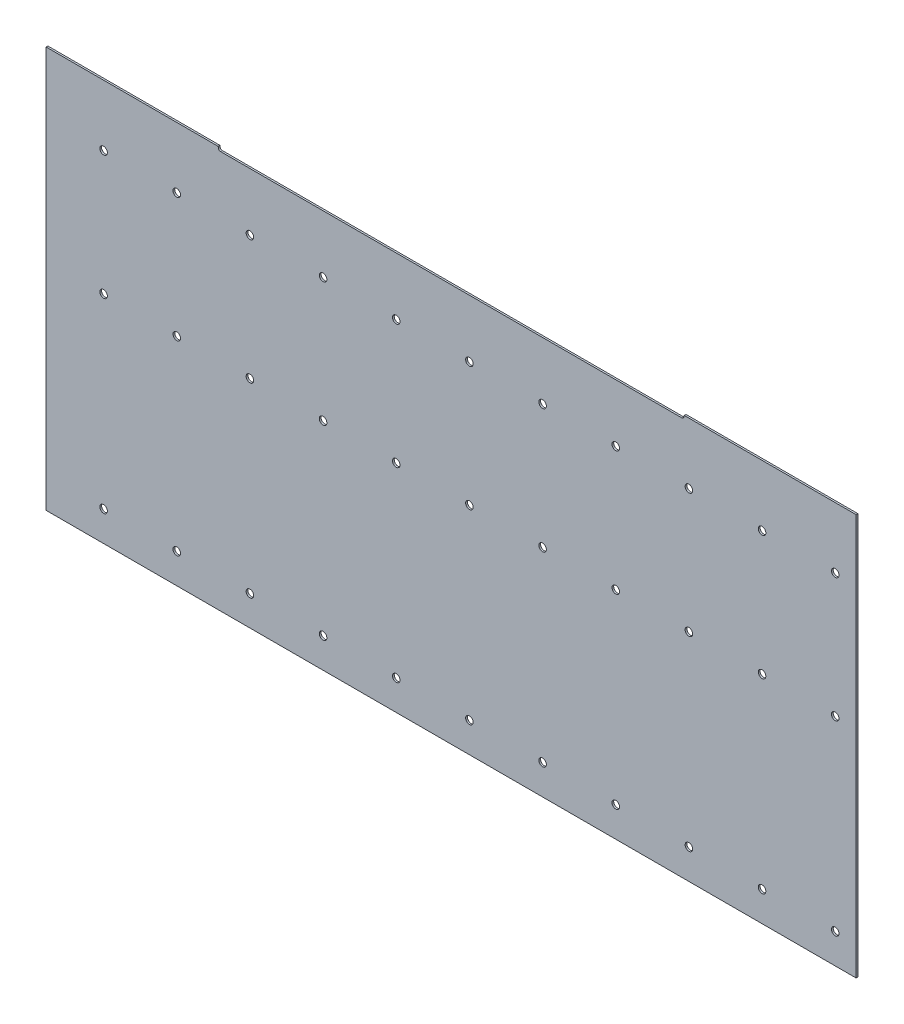
SolidWorks part; units mm, degrees
ref_plane "Plan de face" through (0, 0, 0) normal (0, 0, 1) x (1, 0, 0)
ref_plane "Plan de dessus" through (0, 0, 0) normal (0, 1, 0) x (1, 0, 0)
ref_plane "Plan de droite" through (0, 0, 0) normal (1, 0, 0) x (0, 0, -1)
sketch "Esquisse1" plane through (0, 0, 0) normal (0, 0, 1) x (1, 0, 0)
  line L5 (-182.65, -91) -> (182.65, -91)
  line L6 (-182.65, -91) -> (-182.65, 91)
  line L7 (-182.65, 91) -> (182.65, 91)
  line L8 (182.65, -91) -> (182.65, 91)
  line L9 (-182.65, -91) -> (182.65, 91) construction
  line L10 (-182.65, 91) -> (182.65, -91) construction
  point P0 (0, 0)
  dimension "D1" = 182
  dimension "D2" = 365.3
extrude "Boss.-Extru.1" add sketch "Esquisse1" along normal mid plane 0.7937
sketch "Esquisse2" plane through (0, 0, 0.3969) normal (0, 0, 1) x (1, 0, 0)
  line L0 (-156.75, 7) -> (-156.75, -77) construction
  line L1 (-182.65, 91) -> (-182.65, -91) construction
  line L2 (182.65, 91) -> (-182.65, 91) construction
  circle A0 centre (-156.75, 63) radius 1.7
  circle A1 centre (-156.75, 7) radius 1.7
  circle A2 centre (-156.75, -77) radius 1.7
  dimension "D3" = 3.4
  dimension "D4" = 28
  dimension "D5" = 84
  dimension "D6" = 168
  dimension "D1" = 25.9
  dimension "D2" = 25.9
extrude "Enlèv. mat.-Extru.1" cut sketch "Esquisse2" against normal blind 10
pattern_linear "Répétition linéaire1" count 11 spacing 33 along (1, 0, 0) of "Enlèv. mat.-Extru.1"
sketch "Esquisse3" plane through (0, 0, 0.3969) normal (0, 0, 1) x (1, 0, 0)
  line L0 (182.65, 91) -> (-182.65, 91) construction
  line L1 (-105, 91) -> (105, 91)
  line L2 (-105, 91) -> (-105, 89)
  line L3 (-105, 89) -> (105, 89)
  line L4 (105, 91) -> (105, 89)
  point P6 (0, 89)
  dimension "D1" = 210
  dimension "D2" = 2
extrude "Enlèv. mat.-Extru.2" cut sketch "Esquisse3" against normal through all
fillet "Congé1" radius 1 4 edges at (105, 91, 0) (105, 89, 0) (-105, 89, 0) (-105, 91, 0)
sketch "Esquisse4" plane through (0, 0, 0.3969) normal (0, 0, 1) x (1, 0, 0)
  line L0 (182.65, -91) -> (182.65, 91) construction
  line L1 (-182.65, -90.5) -> (182.65, -90.5)
  line L2 (-182.65, -90.5) -> (-182.65, 90.5)
  line L3 (-182.65, 90.5) -> (182.65, 90.5)
  line L4 (182.65, -90.5) -> (182.65, 90.5)
  line L5 (-182.65, -90.5) -> (182.65, 90.5) construction
  line L6 (-182.65, 90.5) -> (182.65, -90.5) construction
  line L7 (182.65, 91) -> (106, 91) construction
  point P0 (0, 0)
  dimension "D1" = 0.5
extrude "Enlèv. mat.-Extru.3" cut sketch "Esquisse4" against normal through all flip side to cut
